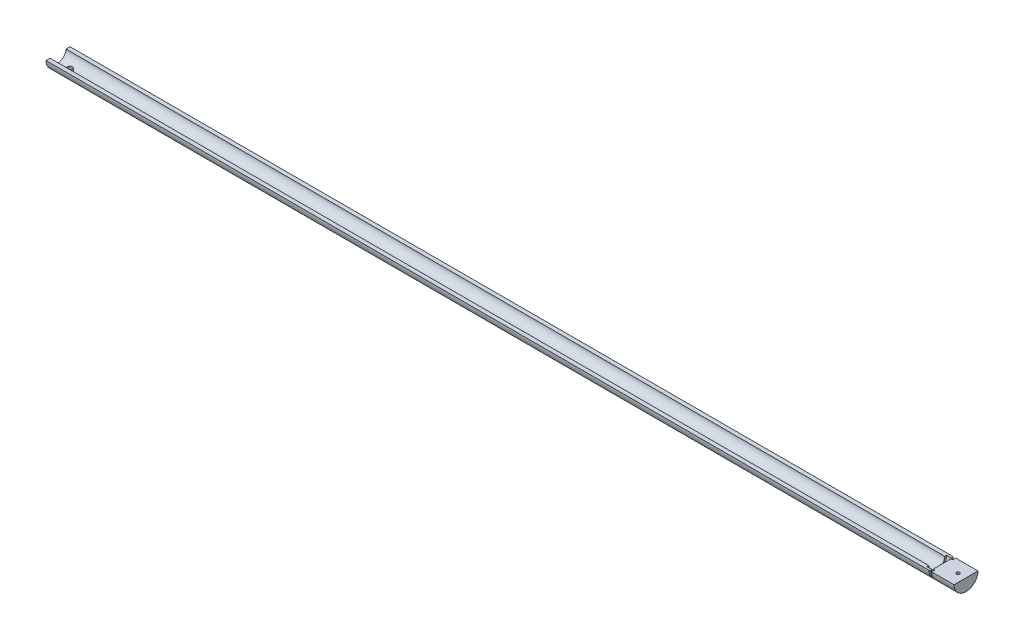
SolidWorks part; units mm, degrees
ref_plane "Front Plane" through (0, 0, 0) normal (0, 0, 1) x (1, 0, 0)
ref_plane "Top Plane" through (0, 0, 0) normal (0, 1, 0) x (1, 0, 0)
ref_plane "Right Plane" through (0, 0, 0) normal (1, 0, 0) x (0, 0, -1)
sketch "Sketch1" plane through (0, 0, 0) normal (0, 1, 0) x (1, 0, 0)
  line L1 (0, 0) -> (1803.4, 0)
  line L2 (0, 0) -> (0, 57.15)
  line L3 (0, 57.15) -> (1803.4, 57.15)
  line L4 (1803.4, 0) -> (1803.4, 57.15)
  dimension "blank_length" = 1803.4
  dimension "blank_width" = 57.15
extrude "wood block" add sketch "Sketch1" along normal blind 28.575
ref_plane "Plane1" through (0, 0, -28.575) normal (0, 0, 1) x (1, 0, 0)
sketch "Sketch2" plane through (0, 0, -28.575) normal (0, 0, 1) x (1, 0, 0)
  line L0 (1755.775, 28.575) -> (0, 28.575)
  line L2 (0, 12.7) -> (1755.775, 12.7)
  line L5 (0, 28.575) -> (0, 0) construction
  line L6 (0, 12.7) -> (0, 28.575)
  line L7 (1755.775, 12.7) -> (1755.775, 28.575)
  dimension "inner_bore_radius" = 15.875
  dimension "finished_length" = 1755.775
revolve "inner bore" cut sketch "Sketch2" angle 360 about L0
sketch "Sketch9" plane through (0, 0, -28.575) normal (0, 0, 1) x (1, 0, 0)
  line L0 (0, 28.575) -> (0, 0) construction
  line L1 (1755.775, 28.575) -> (1745.234, 28.575)
  line L2 (1755.775, 28.575) -> (1755.775, 9.017)
  line L3 (1755.775, 9.017) -> (1745.234, 9.017)
  line L4 (1745.234, 28.575) -> (1745.234, 9.017)
  line L5 (0, 28.575) -> (1803.4, 28.575) construction
  point P7 (1755.775, 28.575)
  point P9 (1745.234, 28.575)
  dimension "flange_foot_recess" = 10.541
  dimension "finished_length" = 1755.775
  dimension "flange_counterbore_radius" = 19.558
revolve "flanged foot relief" cut sketch "Sketch9" angle 360 about L1
ref_axis "Axis1" through (-15.875, 28.575, -28.575) along (1, 0, 0)
sketch "Sketch5" plane through (0, 28.575, 0) normal (0, 1, 0) x (1, 0, 0)
  line L0 (-15.7163, 28.575) -> (15.7163, 28.575) construction
  line L1 (0, 44.45) -> (0, 12.7) construction
  line L2 (15.8369, 28.575) -> (0, 28.575) construction
  line L3 (0, 44.45) -> (0, 12.7) construction
  circle A0 centre (22.225, 28.575) radius 6.3881
  dimension "mouthpiece_hole" = 12.7762
  dimension "mouthpiece_location" = 22.225
extrude "mouthpiece hole" cut sketch "Sketch5" against normal blind 21.59
sketch "Sketch6" plane through (0, 28.575, 0) normal (0, 1, 0) x (1, 0, 0)
  line L0 (1803.4, 28.575) -> (1787.525, 28.575) construction
  line L1 (1803.4, 0) -> (1803.4, 57.15) construction
  circle A1 centre (1787.525, 28.575) radius 3.175
  dimension "dowel_pin_diameter" = 6.35
  dimension "dowel_pin_location" = 15.875
extrude "dowel pin hole" cut sketch "Sketch6" against normal blind 15.24
sketch "Sketch8" plane through (0, 0, 0) normal (0, -1, 0) x (1, 0, 0)
  line L0 (22.225, -28.575) -> (713.359, -28.575) construction
  circle A0 centre (22.225, -28.575) radius 8.128
  circle A1 centre (713.359, -28.575) radius 8.128
  dimension "tube_diameter" = 16.256
  dimension "bracket_length" = 691.134
extrude "mounting holes" cut sketch "Sketch8" against normal blind 10.3124
chamfer "Chamfer1" distance 16.7386 angle 45 2 edges at (901.7, 0, -57.15) (901.7, 0, 0)
sketch "Sketch3" plane through (1803.4, 0, 0) normal (1, 0, 0) x (0, 0, -1)
  line L0 (28.575, 15.7163) -> (28.575, -15.7163) construction
  line L1 (0, 28.575) -> (57.15, 28.575) construction
  circle A0 centre (28.575, 28.575) radius 23.8125
  dimension "outer_diameter" = 47.625
extrude "outer diameter" cut sketch "Sketch3" against normal through all flip side to cut
sketch "Sketch7" plane through (0, 28.575, 0) normal (0, 1, 0) x (1, 0, 0)
  line L0 (1803.4, 4.7625) -> (0, 4.7625) construction
  line L1 (1755.775, 4.7625) -> (1758.95, 4.7625)
  line L2 (1755.775, 4.7625) -> (1755.775, 11.1125)
  line L3 (1755.775, 11.1125) -> (1758.95, 11.1125)
  line L4 (1758.95, 4.7625) -> (1758.95, 11.1125)
  line L5 (1755.775, 12.7) -> (1755.775, 4.7625) construction
  line L6 (1803.4, 4.7625) -> (1803.4, 52.3875) construction
  line L7 (0, 44.45) -> (0, 12.7) construction
  dimension "finished_length" = 1755.775
  dimension "groove_width" = 3.175
  dimension "groove_depth" = 6.35
  dimension "groove_location" = 47.625
revolve "end length locator" cut sketch "Sketch7" angle 360 about axis through (-15.875, 28.575, -28.575) along (1, 0, 0)
chamfer "Chamfer at foot" distance 1.905 angle 45 1 edges at (1755.775, 4.7625, -28.575)
equation "\"g_body_OD\"= 47.625mm"
equation "\"g_body_ID\"= 31.75mm"
equation "\"g_body_L_finished\"= 1755.775mm"
equation "\"g_body_L_blank\"= 1803.4mm"
equation "\"g_body_blank_W\"= 57.15mm"
equation "\"g_dowel_OD\"= 6.35mm"
equation "\"g_thru_passage_OD\"= 12.7mm"
equation "\"g_mp_tube_OD\"= 15.875mm"
equation "\"c_glue_gap\"= 0.0762mm"
equation "\"c_slip_fit\"= 0.381mm"
equation "\"c_dowel_clearance\"= 0mm"
equation "\"thickness@wood block\"= \"g_body_blank_W\" / 2"
equation "\"blank_length@Sketch1\"= \"g_body_L_blank\""
equation "\"blank_width@Sketch1\"= \"g_body_blank_W\""
equation "\"inner_bore_radius@Sketch2\"= \"g_body_ID\" / 2"
equation "\"outer_diameter@Sketch3\"= \"g_body_OD\""
equation "\"finished_length@Sketch7\"= \"g_body_L_finished\""
equation "\"dowel_pin_diameter@Sketch6\"= \"g_dowel_OD\" + \"c_dowel_clearance\""
equation "\"tube_diameter@Sketch8\"= \"g_mp_tube_OD\" + \"c_slip_fit\""
equation "\"mouthpiece_hole@Sketch5\"= \"g_thru_passage_OD\" + \"c_glue_gap\""
